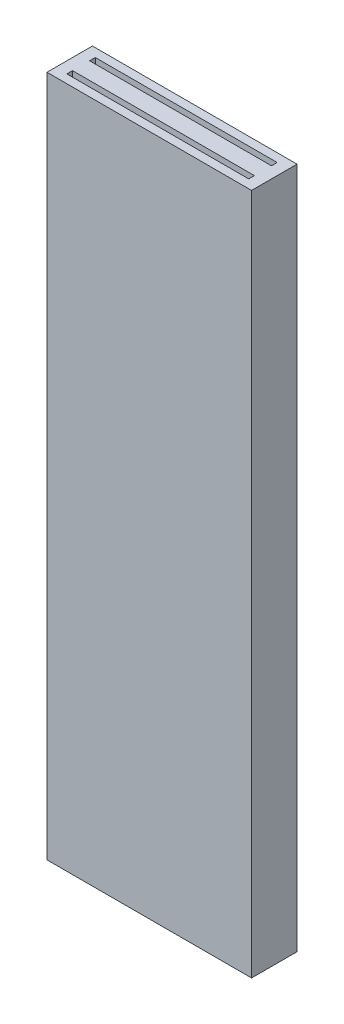
SolidWorks part; units mm, degrees
ref_plane "Front Plane" through (0, 0, 0) normal (0, 0, 1) x (1, 0, 0)
ref_plane "Top Plane" through (0, 0, 0) normal (0, 1, 0) x (1, 0, 0)
ref_plane "Right Plane" through (0, 0, 0) normal (1, 0, 0) x (0, 0, -1)
sketch "Sketch1" plane through (0, 0, 0) normal (0, 1, 0) x (1, 0, 0)
  line L1 (-4.5, -1) -> (4.5, -1)
  line L2 (-4.5, -1) -> (-4.5, 1)
  line L3 (-4.5, 1) -> (4.5, 1)
  line L4 (4.5, -1) -> (4.5, 1)
  line L5 (-4.5, -1) -> (4.5, 1) construction
  line L6 (-4.5, 1) -> (4.5, -1) construction
  point P0 (0, 0)
  dimension "D1" = 9
  dimension "D2" = 2
extrude "Boss-Extrude1" add sketch "Sketch1" along normal mid plane 30
sketch "Sketch2" plane through (0, 15, 0) normal (0, 1, 0) x (1, 0, 0)
  line L1 (-4, 0.375) -> (4, 0.375)
  line L2 (-4, 0.375) -> (-4, 0.625)
  line L3 (-4, 0.625) -> (4, 0.625)
  line L4 (4, 0.375) -> (4, 0.625)
  line L5 (-4, 0.375) -> (4, 0.625) construction
  line L6 (-4, 0.625) -> (4, 0.375) construction
  point P0 (0, 0.5)
  point P7 (0, 0)
  dimension "D1" = 0.25
  dimension "D2" = 8
  dimension "D3" = 0
  dimension "D4" = 0.5
extrude "Cut-Extrude1" cut sketch "Sketch2" against normal through all and the other way through all
mirror "Mirror1" about plane through (0, 0, 0) normal (0, 0, 1) of "Cut-Extrude1"
